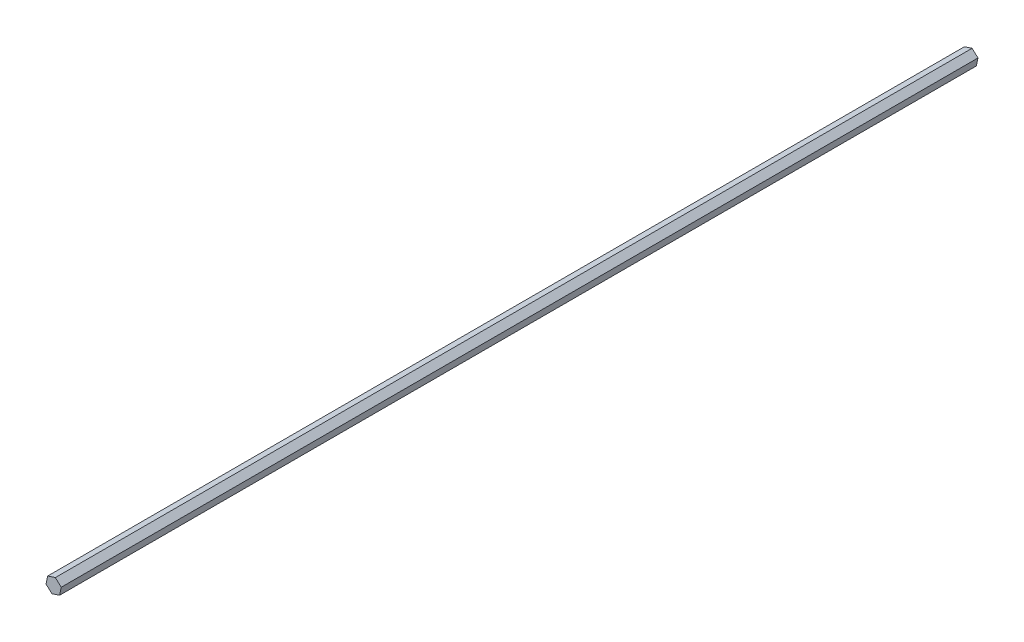
SolidWorks part; units mm, degrees
ref_plane "Front Plane" through (0, 0, 0) normal (0, 0, 1) x (1, 0, 0)
ref_plane "Top Plane" through (0, 0, 0) normal (0, 1, 0) x (1, 0, 0)
ref_plane "Right Plane" through (0, 0, 0) normal (1, 0, 0) x (0, 0, -1)
sketch "Sketch1" plane through (0, 0, 0) normal (0, 0, 1) x (1, 0, 0)
  line L1 (2.1373, -1.9404) -> (2.7491, 0.8807)
  line L2 (2.7491, 0.8807) -> (0.6118, 2.8212)
  line L3 (0.6118, 2.8212) -> (-2.1373, 1.9404)
  line L4 (-2.1373, 1.9404) -> (-2.7491, -0.8807)
  line L5 (-2.7491, -0.8807) -> (-0.6118, -2.8212)
  line L6 (-0.6118, -2.8212) -> (2.1373, -1.9404)
  circle A0 centre (0, 0) radius 2.5 construction
extrude "Boss-Extrude1" add sketch "Sketch1" along normal blind 330.2
